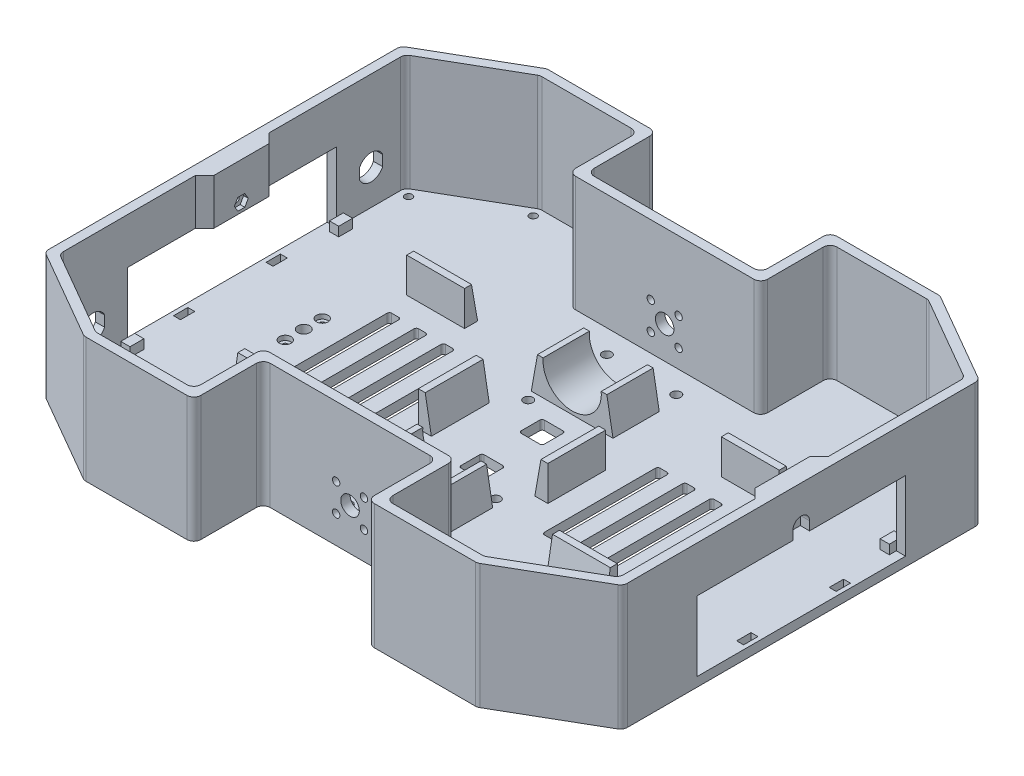
SolidWorks part; units mm, degrees
ref_plane "Front Plane" through (0, 0, 0) normal (0, 0, 1) x (1, 0, 0)
ref_plane "Top Plane" through (0, 0, 0) normal (0, 1, 0) x (1, 0, 0)
ref_plane "Right Plane" through (0, 0, 0) normal (1, 0, 0) x (0, 0, -1)
sketch "Sketch1" plane through (0, 0, 0) normal (0, 1, 0) x (1, 0, 0)
  line L0 (-85, 100) -> (85, 100)
  line L1 (-125, 100) -> (125, 100) construction
  line L2 (-125, 100) -> (-125, -100) construction
  line L3 (-125, -100) -> (125, -100) construction
  line L4 (125, 100) -> (125, -100) construction
  line L5 (85, 100) -> (125, 76.906)
  line L6 (125, 76.906) -> (125, -76.906)
  line L8 (-125, -76.906) -> (-125, 76.906)
  line L9 (-125, 76.906) -> (-85, 100)
  line L10 (-125, 0) -> (125, 0) construction
  line L11 (85, -100) -> (125, -76.906)
  line L12 (-85, -100) -> (85, -100)
  line L13 (-125, -76.906) -> (-85, -100)
  point P4 (0, 100)
  point P6 (-125, 0)
  point P9 (0, 0)
  dimension "D1" = 250
  dimension "D2" = 200
  dimension "D3" = 60
  dimension "D4" = 60
  dimension "D5" = 40
extrude "Boss-Extrude1" add sketch "Sketch1" along normal blind 54
shell "Shell1" thickness 4 removed face at (0, 54, 0)
sketch "Sketch7" plane through (0, 54, 0) normal (0, 1, 0) x (1, 0, 0)
  line L0 (-85, -100) -> (85, -100) construction
  line L1 (-37.5, -70) -> (37.5, -70)
  line L2 (-37.5, -70) -> (-37.5, -100)
  line L3 (-37.5, -100) -> (37.5, -100)
  line L4 (37.5, -70) -> (37.5, -100)
  point P6 (0, -70)
  dimension "D1" = 30
  dimension "D2" = 75
extrude "Cut-Extrude4" cut sketch "Sketch7" against normal up to next
sketch "Sketch8" plane through (0, 4, 0) normal (0, 1, 0) x (1, 0, 0)
  line L0 (-37.5, -96) -> (-37.5, -70)
  line L1 (-37.5, -70) -> (37.5, -70)
  line L2 (37.5, -70) -> (37.5, -96)
  line L3 (-41.5, -96) -> (-41.5, -66)
  line L4 (-41.5, -66) -> (41.5, -66)
  line L5 (41.5, -66) -> (41.5, -96)
  line L6 (-37.5, -96) -> (-41.5, -96)
  line L7 (37.5, -96) -> (41.5, -96)
  dimension "D1" = 4
extrude "Boss-Extrude3" add sketch "Sketch8" along normal up to surface (50 mm away) contours L3 L4 L5 L7 L2 L1 L0 L6 up to face at (0, 54, 19.6)
sketch "Sketch9" plane through (0, 0, 70) normal (0, 0, 1) x (1, 0, 0)
  line B0 (6.0104, 11.9896) -> (-6.0104, 24.0104) construction
  circle B1 centre (0, 18) radius 4
  circle B2 centre (6.0104, 11.9896) radius 1.6
  circle B3 centre (-6.0104, 24.0104) radius 1.6
  circle B4 centre (0, 18) radius 12.5 construction
  line B5 (-6.0104, 11.9896) -> (6.0104, 24.0104) construction
  circle B6 centre (0, 18) radius 4
  circle B7 centre (-6.0104, 11.9896) radius 1.6
  circle B8 centre (6.0104, 24.0104) radius 1.6
  circle B9 centre (0, 18) radius 12.5 construction
  dimension "D1" = 18
sketch_block_instance "Block-JGA25-371-1"
sketch_block "Block1" parameters "D1"=8, "D3"=3.2, "D4"=25, "D2"=17
sketch_block_instance "Block1-1"
extrude "Cut-Extrude5" cut sketch "Sketch9" against normal up to surface (4 mm away) contours B1 | B7 | B3 | B8 | B2 region at (0, 18, 70) region at (6.0104, 11.9896, 70) region at (-6.0104, 24.0104, 70) region at (-6.0104, 11.9896, 70) region at (6.0104, 24.0104, 70) up to face at (0, 29, 66)
sketch "Sketch10" plane through (0, 4, 0) normal (0, 1, 0) x (1, 0, 0)
  line L0 (41.5, -66) -> (-41.5, -66) construction
  line L1 (-15, -26) -> (15, -26)
  line L2 (-15, -26) -> (-15, -46)
  line L3 (-15, -46) -> (15, -46)
  line L4 (15, -26) -> (15, -46)
  point P6 (0, -26)
  dimension "D1" = 30
  dimension "D2" = 20
  dimension "D3" = 20
extrude "Boss-Extrude4" add sketch "Sketch10" along normal blind 15
sketch "Sketch11" plane through (0, 0, 46) normal (0, 0, 1) x (1, 0, 0)
  circle A0 centre (0, 18) radius 12.6
  dimension "D1" = 25.2
extrude "Cut-Extrude6" cut sketch "Sketch11" against normal up to surface (20 mm away) up to face at (0, 11.5, 26)
sketch "Sketch12" plane through (0, 4, 0) normal (0, 1, 0) x (1, 0, 0)
  line L0 (-41.5, -66) -> (41.5, -66) construction
  line L1 (-5, -8) -> (5, -8)
  line L2 (-5, -8) -> (-5, -18)
  line L3 (-5, -18) -> (5, -18)
  line L4 (5, -8) -> (5, -18)
  point P4 (0, -8)
  dimension "D1" = 10
  dimension "D2" = 48
extrude "Cut-Extrude7" cut sketch "Sketch12" against normal through all
fillet "Fillet1" radius 1 4 edges at (-5, 2, 18) (5, 2, 18) (5, 2, 8) (-5, 2, 8)
chamfer "Chamfer1" distance 15 angle 10 2 edges at (-15, 4, 36) (15, 4, 36) first distance on face at (-15, 11.5, 36) first distance on face at (15, 11.5, 36)
sketch "Sketch36" plane through (0, 4, 0) normal (0, 1, 0) x (1, 0, 0)
  line L0 (15, -56) -> (-15, -56) construction
  line L1 (-41.5, -66) -> (41.5, -66) construction
  line L2 (-15, -22) -> (15, -22) construction
  circle A0 centre (15, -56) radius 2
  circle A1 centre (-15, -56) radius 2
  circle A2 centre (-15, -22) radius 2
  circle A3 centre (15, -22) radius 2
  point P4 (0, -56)
  dimension "D1" = 4
  dimension "D2" = 30
  dimension "D3" = 10
  dimension "D4" = 34
extrude "Cut-Extrude22" cut sketch "Sketch36" against normal up to next
mirror "Mirror2" about plane through (0, 0, 0) normal (0, 0, 1) of "Cut-Extrude22", "Fillet1", "Cut-Extrude7", "Cut-Extrude5", "Boss-Extrude3", "Cut-Extrude4", "Cut-Extrude6", "Boss-Extrude4", "Chamfer1"
sketch "Sketch13" plane through (0, 4, 0) normal (0, 1, 0) x (1, 0, 0)
  line L0 (-90, 0) -> (90, 0) construction
  circle A0 centre (-90, 0) radius 2.6
  circle A1 centre (90, 0) radius 2.6
  point P2 (0, 0)
  circle B0 centre (-90.0005, -8) radius 1.1
  circle B1 centre (-89.9995, 8) radius 1.1
  circle B2 centre (89.9995, -8) radius 1.1
  circle B3 centre (90.0005, 8) radius 1.1
  dimension "D2" = 5.2
  dimension "D1" = 180
sketch_block_instance "Ball-Caster-1"
sketch_block "Ball-Caster" parameters "D1"=16, "D2"=2.2, "D3"=16
sketch_block_instance "Ball-Caster-2"
extrude "Cut-Extrude8" cut sketch "Sketch13" against normal blind 10
sketch "Sketch14" plane through (0, 4, 0) normal (0, 1, 0) x (1, 0, 0)
  circle A0 centre (-89.9995, 8) radius 2.5
  circle A1 centre (-90.0005, -8) radius 2.5
  circle A2 centre (90.0005, 8) radius 2.5
  circle A3 centre (89.9995, -8) radius 2.5
  dimension "D1" = 5
extrude "Cut-Extrude9" cut sketch "Sketch14" against normal blind 2
sketch "Sketch16" plane through (-125, 0, 0) normal (-1, 0, 0) x (0, 0, 1)
  line L1 (-45.1, 34.2) -> (45.1, 34.2)
  line L2 (-45.1, 34.2) -> (-45.1, 4)
  line L3 (-45.1, 4) -> (45.1, 4)
  line L4 (45.1, 34.2) -> (45.1, 4)
  line L5 (-76.906, 0) -> (76.906, 0) construction
  point P6 (0, 34.2)
  dimension "D1" = 30.2
  dimension "D2" = 90.2
  dimension "D5" = 4
extrude "Cut-Extrude10" cut sketch "Sketch16" against normal blind 4.2 contours L4 L1 L2 L3 region at (-125, 19.1, 0)
sketch "Sketch19" plane through (0, 4, 0) normal (0, 1, 0) x (1, 0, 0)
  line L0 (-125, 0) -> (0, 0) construction
  line L1 (-123.2, 23.1) -> (-120.2, 23.1)
  line L2 (-123.2, 23.1) -> (-123.2, 16.9)
  line L3 (-123.2, 16.9) -> (-120.2, 16.9)
  line L4 (-120.2, 23.1) -> (-120.2, 16.9)
  line L11 (-125, 45.1) -> (-125, -45.1) construction
  line L12 (-123.2, -16.9) -> (-120.2, -16.9)
  line L13 (-120.2, -23.1) -> (-120.2, -16.9)
  line L14 (-123.2, -23.1) -> (-120.2, -23.1)
  line L15 (-123.2, -23.1) -> (-123.2, -16.9)
  point P6 (-120.2, 20)
  dimension "D1" = 3
  dimension "D2" = 6.2
  dimension "D3" = 1.8
  dimension "D4" = 20
extrude "Cut-Extrude12" cut sketch "Sketch19" against normal up to next
sketch "Sketch26" plane through (-125, 0, 0) normal (-1, 0, 0) x (0, 0, 1)
  line L2 (-45.1, 4) -> (45.1, 4) construction
  line L3 (-76.906, 0) -> (76.906, 0) construction
  line L4 (-45.1, 34.2) -> (45.1, 34.2) construction
  line L5 (-3.6, 38) -> (3.6, 38)
  line L6 (-3.6, 38) -> (-3.6, 34.2)
  line L7 (-3.6, 34.2) -> (3.6, 34.2)
  line L8 (3.6, 38) -> (3.6, 34.2)
  circle A0 centre (0, 38) radius 3.6
  point P5 (0, 0)
  line M13 (-45.1, 34.2) -> (45.1, 34.2)
  dimension "D1" = 7.2
  dimension "D2" = 34
extrude "Cut-Extrude17" cut sketch "Sketch26" against normal up to next contours L5 A0 | L5 A0 | A0 L6 L8 M13 region at (-125, 39.5279, 0) region at (-125, 34.3186, 0) region at (-125, 36.4721, 0)
sketch "Sketch27" plane through (-121, 0, 0) normal (1, 0, 0) x (0, 0, -1)
  line L0 (74.5966, 54) -> (-74.5966, 54) construction
  line L1 (-9.9, 54) -> (9.9, 54)
  line L2 (-9.9, 54) -> (-9.9, 34.2)
  line L3 (-9.9, 34.2) -> (9.9, 34.2)
  line L4 (9.9, 54) -> (9.9, 34.2)
  line L5 (3.6, 34.2) -> (45.1, 34.2) construction
  point P8 (0, 54)
  point P9 (0, 54)
extrude "Boss-Extrude6" add sketch "Sketch27" along normal blind 4
sketch "Sketch28" plane through (-117, 0, 0) normal (1, 0, 0) x (0, 0, -1)
  line L0 (9.9, 54) -> (-9.9, 54) construction
  line L1 (1.5011, 35.4) -> (3.0022, 38)
  line L2 (3.0022, 38) -> (1.5011, 40.6)
  line L3 (1.5011, 40.6) -> (-1.5011, 40.6)
  line L4 (-1.5011, 40.6) -> (-3.0022, 38)
  line L5 (-3.0022, 38) -> (-1.5011, 35.4)
  line L6 (-1.5011, 35.4) -> (1.5011, 35.4)
  circle A0 centre (0, 38) radius 2.6 construction
  point P11 (0, 54)
  dimension "D1" = 5.2
  dimension "D2" = 34
extrude "Cut-Extrude18" cut sketch "Sketch28" against normal blind 2
sketch "Sketch29" plane through (-121, 0, 0) normal (-1, 0, 0) x (0, 0, 1)
  circle A0 centre (0, 38) radius 1.1
  dimension "D1" = 2.2
extrude "Cut-Extrude19" cut sketch "Sketch29" against normal up to next
sketch "Sketch30" plane through (0, 4, 0) normal (0, 1, 0) x (1, 0, 0)
  line L0 (-125, 0) -> (0, 0) construction
  line L1 (-125, 45.1) -> (-125, -45.1) construction
  line L2 (-121, 74.5966) -> (-121, 45.1) construction
  line L3 (-121, 48.1) -> (-117, 48.1)
  line L4 (-121, 48.1) -> (-121, 42.1)
  line L5 (-121, 42.1) -> (-117, 42.1)
  line L6 (-117, 48.1) -> (-117, 42.1)
  line L7 (-121, -42.1) -> (-117, -42.1)
  line L8 (-117, -48.1) -> (-117, -42.1)
  line L9 (-121, -48.1) -> (-117, -48.1)
  line L10 (-121, -48.1) -> (-121, -42.1)
  point P11 (-121, 45.1)
  dimension "D1" = 4
  dimension "D2" = 6
extrude "Boss-Extrude7" add sketch "Sketch30" along normal blind 4
mirror "Mirror4" about plane through (0, 0, 0) normal (1, 0, 0) of "Cut-Extrude12", "Cut-Extrude10", "Cut-Extrude17", "Cut-Extrude19", "Cut-Extrude18", "Boss-Extrude6", "Boss-Extrude7"
chamfer "Chamfer3" distance 6 angle 45 4 edges at (-121, 44.1, 9.9) (-121, 44.1, -9.9) (121, 44.1, 9.9) (121, 44.1, -9.9)
sketch "Sketch33" plane through (0, 4, 0) normal (0, 1, 0) x (1, 0, 0)
  line L0 (0, 66) -> (0, -66) construction
  line L1 (-108, 35) -> (-28, 35) construction
  line L2 (-108, 35) -> (-108, -35) construction
  line L3 (-108, -35) -> (-28, -35) construction
  line L4 (-28, 35) -> (-28, -35) construction
  line L5 (-111, 38) -> (-25, 38) construction
  line L6 (-25, 38) -> (-25, -38) construction
  line L7 (-111, -38) -> (-25, -38) construction
  line L8 (-111, 38) -> (-111, -38) construction
  line L9 (-121, 74.5966) -> (-121, 15.9) construction
  line L10 (-28, -12.5) -> (-25, -12.5)
  line L11 (-28, -12.5) -> (-28, 12.5)
  line L12 (-28, 12.5) -> (-25, 12.5)
  line L13 (-25, -12.5) -> (-25, 12.5)
  line L14 (-55.5, 38) -> (-80.5, 38)
  line L15 (-55.5, 38) -> (-55.5, 35)
  line L16 (-55.5, 35) -> (-80.5, 35)
  line L17 (-80.5, 38) -> (-80.5, 35)
  line L18 (-80.5, -35) -> (-55.5, -35)
  line L19 (-80.5, -35) -> (-80.5, -38)
  line L20 (-80.5, -38) -> (-55.5, -38)
  line L21 (-55.5, -35) -> (-55.5, -38)
  line L26 (-41.5, 66) -> (41.5, 66) construction
  line L27 (-41.5, -66) -> (41.5, -66) construction
  line L28 (80.5, -38) -> (55.5, -38)
  line L29 (55.5, -35) -> (55.5, -38)
  line L30 (80.5, -35) -> (55.5, -35)
  line L31 (80.5, -35) -> (80.5, -38)
  line L32 (28, 12.5) -> (25, 12.5)
  line L33 (25, -12.5) -> (25, 12.5)
  line L34 (28, -12.5) -> (25, -12.5)
  line L35 (28, -12.5) -> (28, 12.5)
  line L36 (55.5, 35) -> (80.5, 35)
  line L37 (80.5, 38) -> (80.5, 35)
  line L38 (55.5, 38) -> (80.5, 38)
  line L39 (55.5, 38) -> (55.5, 35)
  point P4 (-28, 0)
  point P16 (-28, 0)
  point P21 (-68, 35)
  point P22 (-68, 35)
  point P27 (-68, -35)
  point P28 (-68, -35)
  dimension "D1" = 80
  dimension "D2" = 70
  dimension "D3" = 3
  dimension "D4" = 10
  dimension "D5" = 25
extrude "Boss-Extrude9" add sketch "Sketch33" along normal blind 15
chamfer "Chamfer8" distance 15 angle 10 6 edges at (-68, 4, 38) (-25, 4, 0) (-68, 4, -38) (68, 4, -38) (25, 4, 0) (68, 4, 38) first distance on face at (-68, 11.5, 38) first distance on face at (-25, 11.5, 0) first distance on face at (-68, 11.5, -38) first distance on face at (68, 11.5, -38) first distance on face at (25, 11.5, 0) first distance on face at (68, 11.5, 38)
sketch "Sketch31" plane through (0, 54, 0) normal (0, 1, 0) x (1, 0, 0)
  line L0 (-37.5, 100) -> (-85, 100) construction
  line L1 (-55, 100) -> (55, 100)
  line L2 (-55, 100) -> (-55, -100)
  line L3 (-55, -100) -> (55, -100)
  line L4 (55, 100) -> (55, -100)
  line L5 (37.5, -100) -> (85, -100) construction
  point P8 (0, -100)
  dimension "D1" = 110
extrude "Cut-Extrude20" [suppressed] cut sketch "Sketch31" against normal blind 8
chamfer "Chamfer6" [suppressed] distance 8 angle 45
sketch "Sketch34" plane through (-125, 0, 0) normal (-1, 0, 0) x (0, 0, 1)
  line L0 (55.1, 21.3913) -> (55.1, 16.8087)
  line L1 (65.1, 21.3913) -> (65.1, 16.8087)
  line L2 (45.1, 34.2) -> (45.1, 4) construction
  line L3 (-45.1, 34.2) -> (-45.1, 4) construction
  line L4 (0, 54) -> (0, 0) construction
  line L5 (-76.906, 54) -> (76.906, 54) construction
  line L6 (-76.906, 0) -> (76.906, 0) construction
  line L7 (-65.1, 21.3913) -> (-65.1, 16.8087)
  line L8 (-55.1, 21.3913) -> (-55.1, 16.8087)
  circle A0 centre (60.1, 19.1) radius 5.5
  circle A1 centre (-60.1, 19.1) radius 5.5
  point P6 (-45.1, 19.1)
  point P7 (45.1, 19.1)
  dimension "D1" = 11
  dimension "D2" = 10
  dimension "D3" = 15
extrude "Cut-Extrude21" cut sketch "Sketch34" against normal up to next contours A1 L8 L7 | L1 A0 L0 region at (-125, 19.1, 60.1) region at (-125, 19.1, -60.1)
fillet "Fillet2" radius 3 16 edges at (-37.5, 27, 70) (37.5, 27, 70) (37.5, 27, -70) (-37.5, 27, -70) (-37.5, 27, -100) (-85, 27, -100) (-125, 27, -76.906) (-125, 27, 76.906) (-85, 27, 100) (-37.5, 27, 100) (37.5, 27, 100) (85, 27, 100) (125, 27, 76.906) (125, 27, -76.906) (85, 27, -100) (37.5, 27, -100)
fillet "Fillet3" radius 3 16 edges at (121, 29, -74.5966) (83.9282, 29, -96) (41.5, 29, -96) (41.5, 29, -66) (-41.5, 29, -66) (-41.5, 29, -96) (-83.9282, 29, -96) (-121, 29, -74.5966) (-121, 29, 74.5966) (-83.9282, 29, 96) (-41.5, 29, 96) (-41.5, 29, 66) (41.5, 29, 66) (41.5, 29, 96) (83.9282, 29, 96) (121, 29, 74.5966)
sketch "Sketch37" plane through (0, 4, 0) normal (0, 1, 0) x (1, 0, 0)
  line L0 (125, 0) -> (-125, 0) construction
  line L1 (125, -75.1739) -> (125, 75.1739) construction
  line L2 (-125, 75.1739) -> (-125, -75.1739) construction
  line L3 (0, 70) -> (0, -70) construction
  line L4 (34.5, 70) -> (-34.5, 70) construction
  line L5 (34.5, -70) -> (-34.5, -70) construction
  line L6 (84.1962, 100) -> (40.5, 100) construction
  line L7 (123.5, 77.772) -> (85.6962, 99.5981) construction
  circle A0 centre (82.8564, 92) radius 1.6
  circle A1 centre (117, 72.2872) radius 1.6
  circle A4 centre (117, -72.2872) radius 1.6
  circle A5 centre (82.8564, -92) radius 1.6
  circle A6 centre (-82.8564, -92) radius 1.6
  circle A7 centre (-117, -72.2872) radius 1.6
  circle A8 centre (-117, 72.2872) radius 1.6
  circle A9 centre (-82.8564, 92) radius 1.6
  dimension "D5" = 3.2
  dimension "D1" = 8
  dimension "D2" = 8
  dimension "D3" = 8
  dimension "D4" = 8
extrude "Cut-Extrude23" cut sketch "Sketch37" against normal through all
sketch "Sketch38" plane through (0, 4, 0) normal (0, 1, 0) x (1, 0, 0)
  line L1 (-42, 25) -> (-39, 25)
  line L2 (-43, 24) -> (-43, -24)
  line L3 (-42, -25) -> (-39, -25)
  line L4 (-38, 24) -> (-38, -24)
  line L5 (-28, 12.5) -> (-28, -12.5) construction
  line L6 (-54.6667, 24) -> (-54.6667, -24)
  line L7 (-53.6667, 25) -> (-50.6667, 25)
  line L8 (-49.6667, 24) -> (-49.6667, -24)
  line L9 (-53.6667, -25) -> (-50.6667, -25)
  line L10 (-66.3333, 24) -> (-66.3333, -24)
  line L11 (-65.3333, 25) -> (-62.3333, 25)
  line L12 (-61.3333, 24) -> (-61.3333, -24)
  line L13 (-65.3333, -25) -> (-62.3333, -25)
  line L14 (-78, 24) -> (-78, -24)
  line L15 (-77, 25) -> (-74, 25)
  line L16 (-73, 24) -> (-73, -24)
  line L17 (-77, -25) -> (-74, -25)
  line L18 (0, 66) -> (0, -66) construction
  line L19 (-38.5, 66) -> (38.5, 66) construction
  line L20 (-38.5, -66) -> (38.5, -66) construction
  line L22 (77, -25) -> (74, -25)
  line L23 (73, 24) -> (73, -24)
  line L24 (77, 25) -> (74, 25)
  line L25 (78, 24) -> (78, -24)
  line L26 (65.3333, -25) -> (62.3333, -25)
  line L27 (61.3333, 24) -> (61.3333, -24)
  line L28 (65.3333, 25) -> (62.3333, 25)
  line L29 (66.3333, 24) -> (66.3333, -24)
  line L30 (53.6667, -25) -> (50.6667, -25)
  line L31 (49.6667, 24) -> (49.6667, -24)
  line L32 (53.6667, 25) -> (50.6667, 25)
  line L33 (54.6667, 24) -> (54.6667, -24)
  line L34 (38, 24) -> (38, -24)
  line L35 (42, -25) -> (39, -25)
  line L36 (43, 24) -> (43, -24)
  line L37 (42, 25) -> (39, 25)
  arc A0 (-42, 25) -> (-43, 24) centre (-42, 24) ccw
  arc A1 (-39, 25) -> (-38, 24) centre (-39, 24) cw
  arc A2 (-39, -25) -> (-38, -24) centre (-39, -24) ccw
  arc A3 (-43, -24) -> (-42, -25) centre (-42, -24) ccw
  arc A4 (-54.6667, -24) -> (-53.6667, -25) centre (-53.6667, -24) ccw
  arc A5 (-49.6667, -24) -> (-50.6667, -25) centre (-50.6667, -24) cw
  arc A6 (-50.6667, 25) -> (-49.6667, 24) centre (-50.6667, 24) cw
  arc A7 (-54.6667, 24) -> (-53.6667, 25) centre (-53.6667, 24) cw
  arc A8 (-66.3333, 24) -> (-65.3333, 25) centre (-65.3333, 24) cw
  arc A9 (-62.3333, 25) -> (-61.3333, 24) centre (-62.3333, 24) cw
  arc A10 (-61.3333, -24) -> (-62.3333, -25) centre (-62.3333, -24) cw
  arc A11 (-66.3333, -24) -> (-65.3333, -25) centre (-65.3333, -24) ccw
  arc A12 (-78, -24) -> (-77, -25) centre (-77, -24) ccw
  arc A13 (-73, -24) -> (-74, -25) centre (-74, -24) cw
  arc A14 (-78, 24) -> (-77, 25) centre (-77, 24) cw
  arc A15 (-74, 25) -> (-73, 24) centre (-74, 24) cw
  arc A16 (74, 25) -> (73, 24) centre (74, 24) ccw
  arc A17 (78, 24) -> (77, 25) centre (77, 24) ccw
  arc A18 (73, -24) -> (74, -25) centre (74, -24) ccw
  arc A19 (78, -24) -> (77, -25) centre (77, -24) cw
  arc A20 (66.3333, -24) -> (65.3333, -25) centre (65.3333, -24) cw
  arc A21 (61.3333, -24) -> (62.3333, -25) centre (62.3333, -24) ccw
  arc A22 (62.3333, 25) -> (61.3333, 24) centre (62.3333, 24) ccw
  arc A23 (66.3333, 24) -> (65.3333, 25) centre (65.3333, 24) ccw
  arc A24 (54.6667, 24) -> (53.6667, 25) centre (53.6667, 24) ccw
  arc A25 (50.6667, 25) -> (49.6667, 24) centre (50.6667, 24) ccw
  arc A26 (49.6667, -24) -> (50.6667, -25) centre (50.6667, -24) ccw
  arc A27 (54.6667, -24) -> (53.6667, -25) centre (53.6667, -24) cw
  arc A28 (43, -24) -> (42, -25) centre (42, -24) cw
  arc A29 (39, -25) -> (38, -24) centre (39, -24) cw
  arc A30 (39, 25) -> (38, 24) centre (39, 24) ccw
  arc A31 (42, 25) -> (43, 24) centre (42, 24) cw
  point P4 (-38, 0)
  point P22 (-43, 25)
  point P25 (-38, 25)
  point P30 (-43, -25)
  point P109 (43, -25)
  point P110 (38, 25)
  point P111 (43, 25)
  dimension "D5" = 1
  dimension "D1" = 5
  dimension "D2" = 50
  dimension "D3" = 10
  dimension "D4" = 4
extrude "Cut-Extrude24" cut sketch "Sketch38" against normal through all
